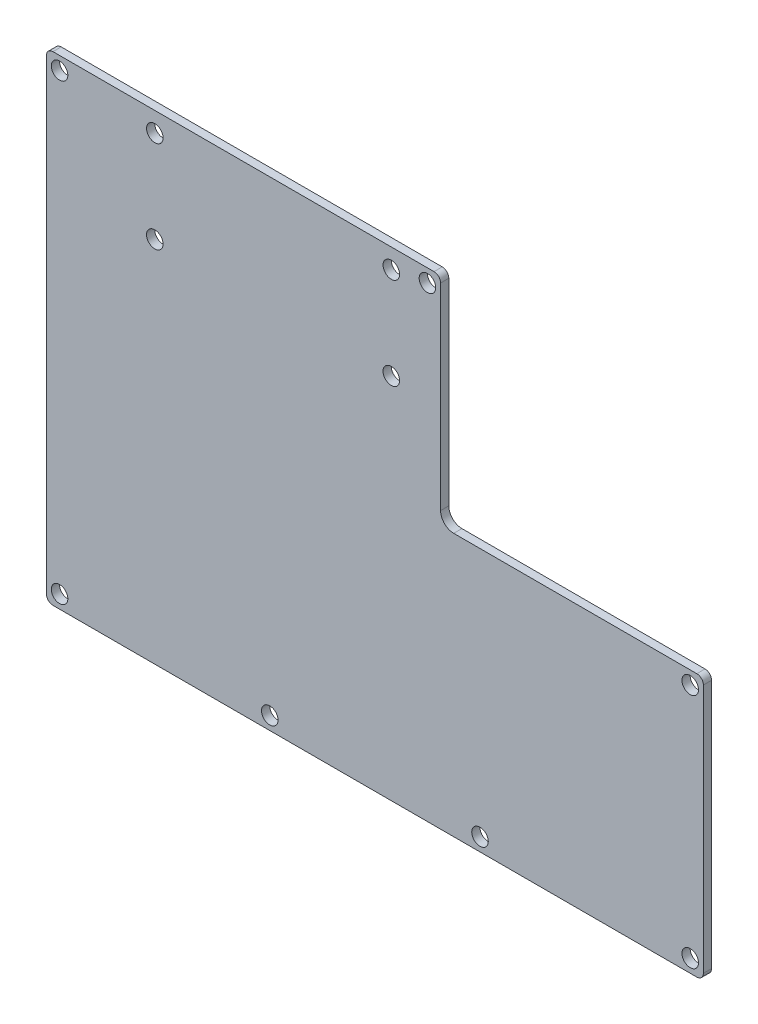
SolidWorks part; units mm, degrees
ref_plane "Front" through (0, 0, 0) normal (0, 0, 1) x (1, 0, 0)
ref_plane "Top" through (0, 0, 0) normal (0, 1, 0) x (1, 0, 0)
ref_plane "Right" through (0, 0, 0) normal (1, 0, 0) x (0, 0, -1)
sketch "Model" plane through (0, 0, 0) normal (0, 0, 1) x (1, 0, 0)
  line L0 (127, 49.53) -> (127, 1.27)
  line L1 (0, 91.44) -> (0, 1.27)
  line L2 (1.27, 0) -> (125.73, 0)
  line L3 (1.27, 92.71) -> (74.93, 92.71)
  line L4 (76.2, 91.44) -> (76.2, 53.34)
  line L5 (78.74, 50.8) -> (125.73, 50.8)
  arc A0 (125.73, 0) -> (127, 1.27) centre (125.73, 1.27) ccw
  arc A1 (0, 1.27) -> (1.27, 0) centre (1.27, 1.27) ccw
  arc A2 (76.2, 91.44) -> (74.93, 92.71) centre (74.93, 91.44) ccw
  arc A3 (1.27, 92.71) -> (0, 91.44) centre (1.27, 91.44) ccw
  arc A4 (76.2, 53.34) -> (78.74, 50.8) centre (78.74, 53.34) ccw
  arc A5 (127, 49.53) -> (125.73, 50.8) centre (125.73, 49.53) ccw
  circle A6 centre (2.54, 2.54) radius 1.6
  circle A7 centre (124.46, 2.54) radius 1.6
  circle A8 centre (2.54, 90.17) radius 1.6
  circle A9 centre (43.18, 2.54) radius 1.6
  circle A10 centre (83.82, 2.54) radius 1.6
  circle A11 centre (73.66, 90.17) radius 1.6
  circle A12 centre (124.46, 48.26) radius 1.6
  circle A13 centre (66.675, 88.9) radius 1.6
  circle A14 centre (20.955, 88.9) radius 1.6
  circle A15 centre (20.955, 71.12) radius 1.6
  circle A16 centre (66.675, 71.12) radius 1.6
extrude "Boss-Extrude1" add sketch "Model" against normal blind 1.5875
